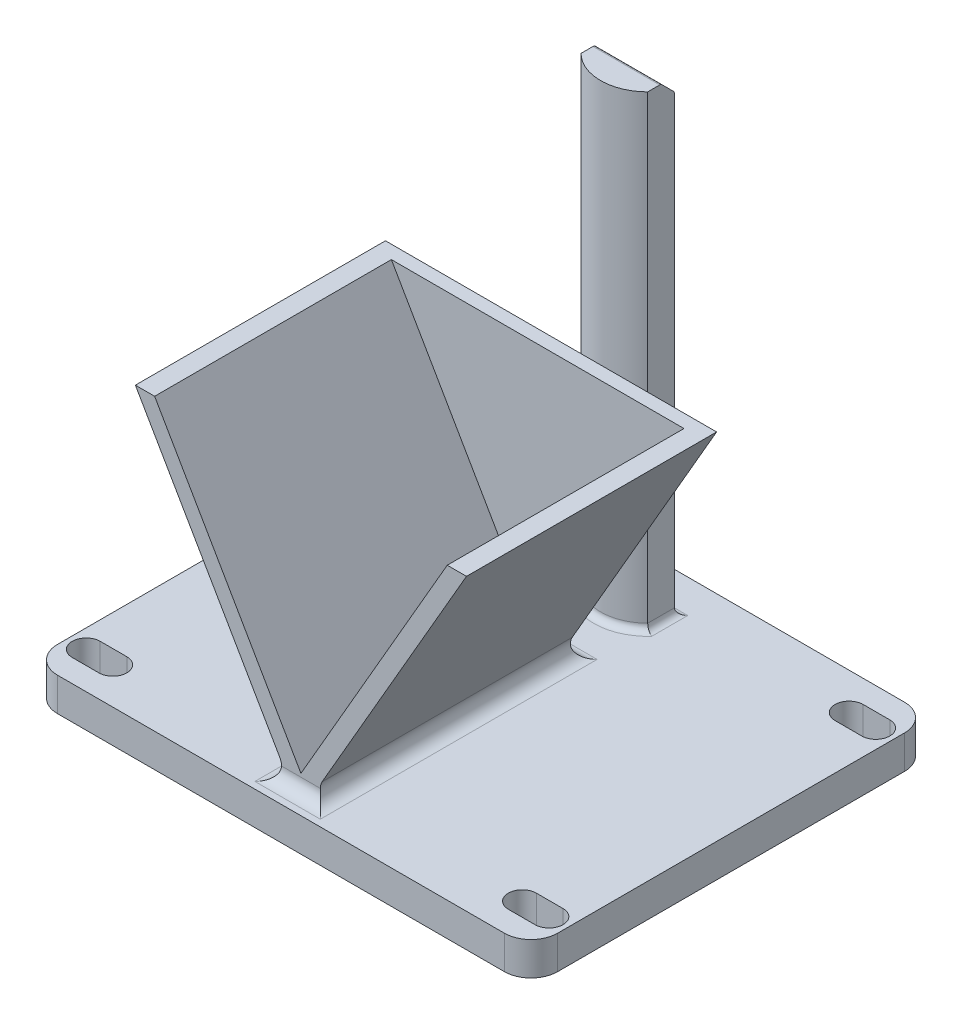
SolidWorks part; units mm, degrees
material "Cast Alloy Steel"
ref_plane "Front Plane" through (0, 0, 0) normal (0, 0, 1) x (1, 0, 0)
ref_plane "Top Plane" through (0, 0, 0) normal (0, 1, 0) x (1, 0, 0)
ref_plane "Right Plane" through (0, 0, 0) normal (1, 0, 0) x (0, 0, -1)
sketch "Sketch1" plane through (0, 0, 0) normal (0, 1, 0) x (1, 0, 0)
  line L1 (-33.5, -30) -> (33.5, -30)
  line L2 (-37.5, -26) -> (-37.5, 26)
  line L3 (-33.5, 30) -> (33.5, 30)
  line L4 (37.5, -26) -> (37.5, 26)
  line L5 (-37.5, -30) -> (37.5, 30) construction
  line L6 (-37.5, 30) -> (37.5, -30) construction
  arc A1 (33.5, -30) -> (37.5, -26) centre (33.5, -26) ccw
  arc A2 (33.5, 30) -> (37.5, 26) centre (33.5, 26) cw
  arc A3 (-37.5, 26) -> (-33.5, 30) centre (-33.5, 26) cw
  arc A4 (-33.5, -30) -> (-37.5, -26) centre (-33.5, -26) cw
  point P0 (0, 0)
  dimension "D2" = 60
  dimension "D3" = 4
  dimension "D4" = 4
  dimension "D1" = 75
extrude "Boss-Extrude1" add sketch "Sketch1" along normal blind 5
sketch "Sketch2" plane through (0, 5, 0) normal (0, 1, 0) x (1, 0, 0)
  line L0 (-36.7206, 0) -> (37.1077, 0) construction
  line L1 (0, 28.7379) -> (0, -20.7068) construction
  circle A0 centre (-29.3668, -23.8031) radius 2.5158
  circle A1 centre (29.3668, -23.8031) radius 2.5158
  circle A2 centre (29.3668, 23.8031) radius 2.5158
  circle A3 centre (-29.3668, 23.8031) radius 2.5158
extrude "Cut-Extrude1" [suppressed] cut sketch "Sketch2" against normal through all
ref_plane "Plane5" through (0, 0, 30) normal (0, 0, 1) x (1, 0, 0)
ref_plane "Plane6" through (0, 0, 27) normal (0, 0, 1) x (1, 0, 0)
sketch "Sketch11" plane through (0, 0, 27) normal (0, 0, 1) x (1, 0, 0)
  line L1 (0, 7.5) -> (21.9393, 45.5)
  line L2 (0, 9.3677) -> (0, 21.2728) construction
  line L5 (1.4434, 5) -> (24.8261, 45.5)
  line L6 (0, 7.5) -> (-21.9393, 45.5)
  line L7 (-33.5, 5) -> (33.5, 5) construction
  line L9 (-1.4434, 5) -> (-24.8261, 45.5)
  line L10 (-1.4434, 5) -> (1.4434, 5)
  line L11 (0, 2.5) -> (24.8261, 45.5) construction
  line L12 (0, 2.5) -> (-24.8261, 45.5) construction
  line L13 (-24.8261, 45.5) -> (-21.9393, 45.5)
  line L14 (0, 7.5) -> (-22.661, 46.75) construction
  line L15 (24.8261, 45.5) -> (21.9393, 45.5)
  line L16 (0, 7.5) -> (22.661, 46.75) construction
  dimension "D1" = 2.5
  dimension "D2" = 30
  dimension "D3" = 30
  dimension "D4" = 2.5
  dimension "D5" = 0
extrude "Boss-Extrude2" add sketch "Sketch11" against normal blind 37.5
sketch "Sketch13" plane through (0, 0, -10.5) normal (0, 0, -1) x (-1, 0, 0)
  line L0 (-24.8261, 45.5) -> (24.8261, 45.5)
  line L1 (24.8261, 45.5) -> (1.4434, 5)
  line L2 (1.4434, 5) -> (-1.4434, 5)
  line L3 (1.4434, 5) -> (-1.4434, 5) construction
  line L4 (-1.4434, 5) -> (-24.8261, 45.5)
extrude "Boss-Extrude4" add sketch "Sketch13" against normal blind 2
fillet "Fillet3" radius 2 1 edges at (-1.4434, 5, 8.25)
fillet "Fillet4" radius 2 1 edges at (1.4434, 5, 8.25)
fillet "Fillet5" radius 2 1 edges at (0, 5, 27)
fillet "Fillet6" radius 2 1 edges at (0, 5, -10.5)
sketch "Sketch14" plane through (0, 5, 0) normal (0, 1, 0) x (1, 0, 0)
  line L8 (-5, 20) -> (-5, 24)
  line L9 (-5, 24) -> (5, 24)
  line L10 (5, 20) -> (5, 24)
  line L11 (-5, 20) -> (5, 24) construction
  line L12 (-5, 24) -> (5, 20) construction
  line L13 (33.5, 30) -> (-33.5, 30) construction
  line L14 (-37.5, 26) -> (-37.5, -26) construction
  arc A0 (-5, 20) -> (5, 20) centre (0, 25) ccw
  point P0 (0, 22)
  dimension "D1" = 37.5
  dimension "D2" = 6
  dimension "D6" = 10
  dimension "D7" = 4
extrude "Boss-Extrude5" add sketch "Sketch14" along normal blind 70
fillet "Fillet7" radius 1 4 edges at (5, 5, -22) (0, 5, -17.9289) (-5, 5, -22) (0, 5, -24)
chamfer "Chamfer2" distance 2 angle 45 1 edges at (0, 75, -24)
fillet "Fillet8" radius 0.5 1 edges at (0, 73, -24)
fillet "Fillet9" radius 0.5 1 edges at (0, 75, -22)
sketch "Sketch15" plane through (0, 5, 0) normal (0, 1, 0) x (1, 0, 0)
  line L0 (-34.7, -24.5) -> (-30.7, -24.5) construction
  line L1 (-34.7, -22.4) -> (-30.7, -22.4)
  line L2 (0, 28.273) -> (0, -17.8813) construction
  line L3 (-36.0717, 0) -> (36.8311, 0) construction
  line L4 (-34.7, -26.6) -> (-30.7, -26.6)
  line L5 (-33.5, -30) -> (33.5, -30) construction
  line L8 (34.7, -24.5) -> (30.7, -24.5) construction
  line L11 (34.7, -22.4) -> (30.7, -22.4)
  line L14 (-37.5, 26) -> (-37.5, -26) construction
  line L18 (34.7, -26.6) -> (30.7, -26.6)
  line L21 (-34.7, 24.5) -> (-30.7, 24.5) construction
  line L24 (-34.7, 22.4) -> (-30.7, 22.4)
  line L25 (-34.7, 26.6) -> (-30.7, 26.6)
  line L26 (34.7, 24.5) -> (30.7, 24.5) construction
  line L27 (34.7, 22.4) -> (30.7, 22.4)
  line L28 (34.7, 26.6) -> (30.7, 26.6)
  arc A3 (-34.7, -22.4) -> (-34.7, -26.6) centre (-34.7, -24.5) ccw
  arc A4 (-30.7, -26.6) -> (-30.7, -22.4) centre (-30.7, -24.5) ccw
  arc A17 (34.7, -22.4) -> (34.7, -26.6) centre (34.7, -24.5) cw
  arc A18 (30.7, -26.6) -> (30.7, -22.4) centre (30.7, -24.5) cw
  arc A19 (-34.7, 22.4) -> (-34.7, 26.6) centre (-34.7, 24.5) cw
  arc A20 (-30.7, 26.6) -> (-30.7, 22.4) centre (-30.7, 24.5) cw
  arc A21 (34.7, 22.4) -> (34.7, 26.6) centre (34.7, 24.5) ccw
  arc A22 (30.7, 26.6) -> (30.7, 22.4) centre (30.7, 24.5) ccw
  point P2 (-32.7, -24.5)
  point P16 (32.7, -24.5)
  point P23 (-32.7, 24.5)
  point P30 (32.7, 24.5)
  point P33 (0, 0)
  dimension "D3" = 2.8
  dimension "D4" = 5.5
  dimension "D1" = 4.2
  dimension "D2" = 4
extrude "Cut-Extrude2" cut sketch "Sketch15" against normal through all
